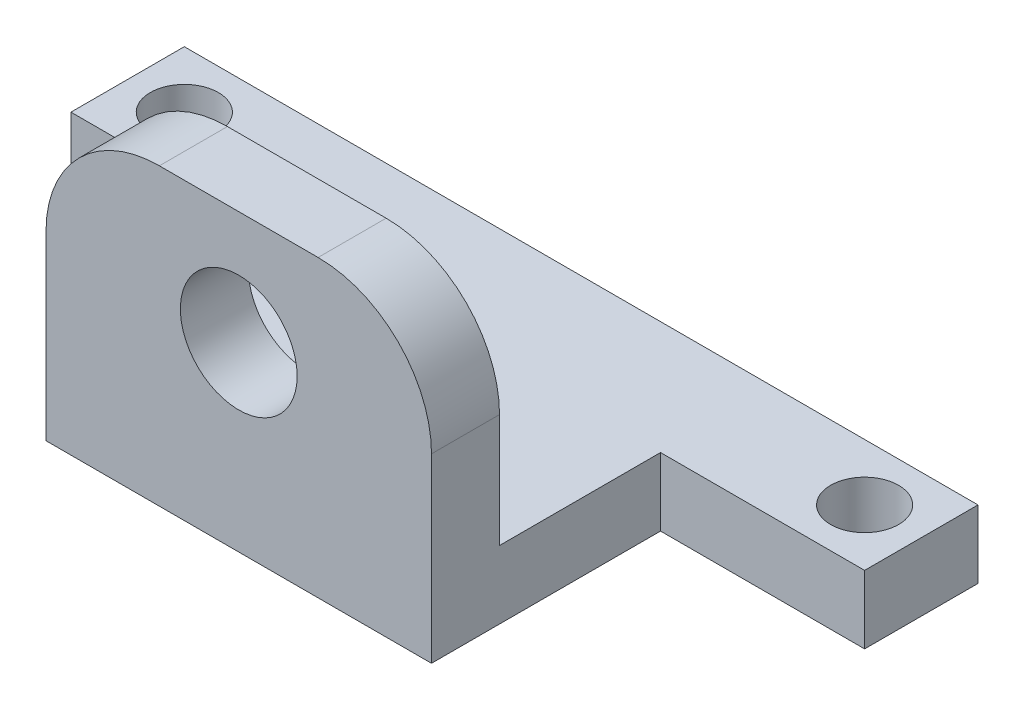
SolidWorks part; units mm, degrees
ref_plane "Front Plane" through (0, 0, 0) normal (0, 0, 1) x (1, 0, 0)
ref_plane "Top Plane" through (0, 0, 0) normal (0, 1, 0) x (1, 0, 0)
ref_plane "Right Plane" through (0, 0, 0) normal (1, 0, 0) x (0, 0, -1)
sketch "Sketch1" plane through (0, 0, 0) normal (1, 0, 0) x (0, 0, -1)
  line L0 (0, 0) -> (31.1, 0)
  line L1 (31.1, 0) -> (31.1, 3)
  line L2 (31.1, 3) -> (3, 3)
  line L3 (3, 3) -> (3, 13)
  line L4 (3, 13) -> (0, 13)
  line L5 (0, 13) -> (0, 0)
  dimension "D1" = 3
  dimension "D2" = 13
  dimension "D3" = 31.1
extrude "Boss-Extrude1" add sketch "Sketch1" along normal blind 17
sketch "Sketch2" plane through (0, 0, 0) normal (0, 0, 1) x (1, 0, 0)
  line L0 (0, 0) -> (17, 0) construction
  line L2 (8.5, 0) -> (8.5, 8) construction
  line L3 (17, 13) -> (0, 13) construction
  point P7 (8.5, 8)
  point P13 (8.5, 8)
  dimension "D1" = 5
hole_wizard "Ø5.0mm Dowel Hole1" positions "Sketch2" profile "Sketch3" hole size "Ø5.0" standard "ANSI Metric"
sketch "Sketch3" plane through (8.5, 8, 0) normal (1, 0, 0) x (0, -1, 0)
  line L0 (0, 0) -> (0, 4.5472)
  line L1 (0, 4.5472) -> (2.575, 3)
  line L2 (2.575, 3) -> (2.575, 0)
  line L5 (2.575, 0) -> (0, 0)
  line L10 (0, 4.5472) -> (-2.575, 3) construction
  line L11 (0, -6.35) -> (0, 107.95) construction
  dimension "Hole Dia." = 5.15
  dimension "Hole Depth" = 3
  dimension "Drill Angle" = 118
fillet "Fillet1" radius 5 2 edges at (0, 13, -1.5) (17, 13, -1.5)
sketch "Sketch4" plane through (0, 3, 0) normal (0, 1, 0) x (1, 0, 0)
  line L0 (8.5, 31.1) -> (8.5, 3) construction
  line L1 (17, 31.1) -> (0, 31.1) construction
  line L2 (17, 3) -> (0, 3) construction
  line L4 (17, 22.6) -> (0, 22.6) construction
  line L7 (0, 31.1) -> (0, 3) construction
  line L8 (17, 31.1) -> (17, 3) construction
  point P42 (3.5, 27.6)
  point P45 (3.5, 17.6)
  point P46 (13.5, 17.6)
  point P47 (13.5, 27.6)
  dimension "D1" = 5
  dimension "D2" = 5
  dimension "D3" = 8.5
hole_wizard "M3 Clearance Hole1" positions "Sketch4" profile "Sketch5" hole size "M3" standard "ANSI Metric" end condition through all
sketch "Sketch5" plane through (13.5, 3, -27.6) normal (1, 0, 0) x (0, 0, 1)
  line L0 (0, 0) -> (0, 3)
  line L1 (0, 3) -> (1.8, 3)
  line L2 (1.8, 3) -> (1.8, 0)
  line L5 (1.8, 0) -> (0, 0)
  line L11 (0, -6.35) -> (0, 107.95) construction
  dimension "Thru Hole Dia." = 3.6
  dimension "Thru Hole Depth" = 3
ref_plane "Plane1" through (8.5, 0, 0) normal (-1, 0, 0) x (0, 0, 1)
sketch "Sketch6" plane through (0, 0, 0) normal (0, -1, 0) x (1, 0, 0)
  line L0 (0, 0) -> (0, -31.1) construction
  line L1 (0, -15.1) -> (-9, -15.1)
  line L2 (0, -15.1) -> (0, -10.1)
  line L3 (0, -10.1) -> (-9, -10.1)
  line L4 (-9, -15.1) -> (-9, -10.1)
  circle A1 centre (-6.5, -12.6) radius 1.5
  circle A2 centre (3.5, -17.6) radius 1.8 construction
  dimension "D1" = 3
  dimension "D2" = 10
  dimension "D3" = 5
  dimension "D4" = 2.5
  dimension "D5" = 2.5
  dimension "D6" = 2.5
extrude "Boss-Extrude2" add sketch "Sketch6" against normal blind 3
mirror "Mirror1" about plane through (8.5, 0, 0) normal (-1, 0, 0) of "Boss-Extrude2"
sketch "Sketch7" plane through (0, 3, 0) normal (0, 1, 0) x (1, 0, 0)
  line L1 (0, 31.1) -> (17, 31.1)
  line L2 (0, 31.1) -> (0, 15.1)
  line L3 (0, 15.1) -> (17, 15.1)
  line L4 (17, 31.1) -> (17, 15.1)
extrude "Cut-Extrude1" cut sketch "Sketch7" against normal blind 3
equation "\"Length\"= 31.1"
equation "\"D3@Sketch1\"=\"Length\""
